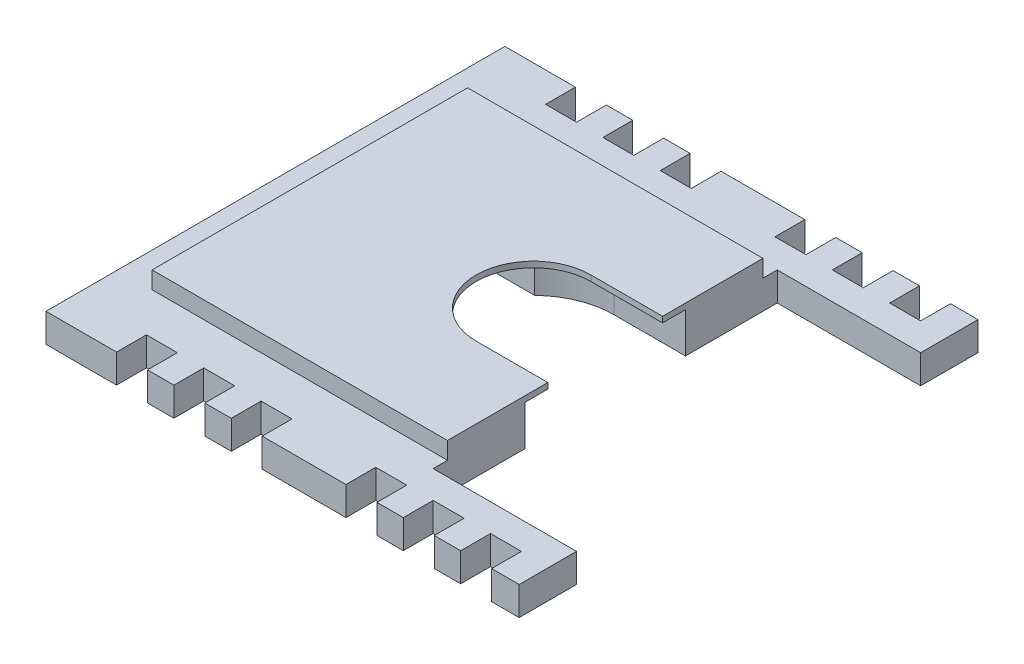
SolidWorks part; units mm, degrees
ref_plane "Front Plane" through (0, 0, 0) normal (0, 0, 1) x (1, 0, 0)
ref_plane "Top Plane" through (0, 0, 0) normal (0, 1, 0) x (1, 0, 0)
ref_plane "Right Plane" through (0, 0, 0) normal (1, 0, 0) x (0, 0, -1)
sketch "Sketch1" plane through (0, 0, 0) normal (0, 1, 0) x (1, 0, 0)
  line L0 (0, -50.8) -> (0, 50.8)
  line L16 (79.375, 34.925) -> (79.375, -34.925)
  line L17 (0, 0) -> (12.404, 0) construction
  line L18 (117.475, 34.925) -> (117.475, 0) construction
  line L19 (104.775, 50.8) -> (104.775, 34.925)
  line L20 (104.775, -34.925) -> (79.375, -34.925)
  line L21 (104.775, -50.8) -> (104.775, -34.925)
  line L22 (98.425, -50.8) -> (104.775, -50.8)
  line L23 (98.425, -44.45) -> (98.425, -50.8)
  line L24 (92.075, -44.45) -> (98.425, -44.45)
  line L25 (92.075, -50.8) -> (92.075, -44.45)
  line L26 (85.725, -50.8) -> (92.075, -50.8)
  line L27 (85.725, -44.45) -> (85.725, -50.8)
  line L29 (28.575, -50.8) -> (28.575, -44.45)
  line L30 (22.225, -50.8) -> (28.575, -50.8)
  line L31 (22.225, -44.45) -> (22.225, -50.8)
  line L32 (15.875, -44.45) -> (22.225, -44.45)
  line L33 (15.875, -50.8) -> (15.875, -44.45)
  line L34 (0, -50.8) -> (15.875, -50.8)
  line L35 (28.575, -44.45) -> (34.925, -44.45)
  line L36 (34.925, -44.45) -> (34.925, -50.8)
  line L37 (34.925, -50.8) -> (41.275, -50.8)
  line L38 (41.275, -50.8) -> (41.275, -44.45)
  line L39 (41.275, -44.45) -> (47.625, -44.45)
  line L40 (79.375, -44.45) -> (79.375, -50.8)
  line L41 (79.375, -50.8) -> (73.025, -50.8)
  line L42 (73.025, -50.8) -> (73.025, -44.45)
  line L43 (79.375, -44.45) -> (85.725, -44.45)
  line L44 (47.625, -44.45) -> (47.625, -50.8)
  line L45 (47.625, -50.8) -> (66.675, -50.8)
  line L46 (66.675, -50.8) -> (66.675, -44.45)
  line L47 (66.675, -44.45) -> (73.025, -44.45)
  line L48 (0, 50.8) -> (15.875, 50.8)
  line L49 (104.775, 34.925) -> (79.375, 34.925)
  line L50 (66.675, 44.45) -> (73.025, 44.45)
  line L51 (66.675, 50.8) -> (66.675, 44.45)
  line L52 (47.625, 50.8) -> (66.675, 50.8)
  line L53 (47.625, 44.45) -> (47.625, 50.8)
  line L54 (79.375, 44.45) -> (85.725, 44.45)
  line L55 (73.025, 50.8) -> (73.025, 44.45)
  line L56 (79.375, 50.8) -> (73.025, 50.8)
  line L57 (79.375, 44.45) -> (79.375, 50.8)
  line L58 (41.275, 44.45) -> (47.625, 44.45)
  line L59 (41.275, 50.8) -> (41.275, 44.45)
  line L60 (34.925, 50.8) -> (41.275, 50.8)
  line L61 (34.925, 44.45) -> (34.925, 50.8)
  line L62 (28.575, 44.45) -> (34.925, 44.45)
  line L63 (15.875, 50.8) -> (15.875, 44.45)
  line L64 (15.875, 44.45) -> (22.225, 44.45)
  line L65 (22.225, 44.45) -> (22.225, 50.8)
  line L66 (22.225, 50.8) -> (28.575, 50.8)
  line L67 (28.575, 50.8) -> (28.575, 44.45)
  line L68 (85.725, 44.45) -> (85.725, 50.8)
  line L69 (85.725, 50.8) -> (92.075, 50.8)
  line L70 (92.075, 50.8) -> (92.075, 44.45)
  line L71 (92.075, 44.45) -> (98.425, 44.45)
  line L72 (98.425, 44.45) -> (98.425, 50.8)
  line L73 (98.425, 50.8) -> (104.775, 50.8)
  circle A0 centre (57.15, 0) radius 12.7
  point P24 (79.375, 0)
  point P44 (57.15, -50.8)
  dimension "D7" = 25.4
  dimension "D1" = 44.45
  dimension "D2" = 6.35
  dimension "D3" = 69.85
  dimension "D4" = 101.6
  dimension "D5" = 25.4
  dimension "D6" = 15.875
extrude "Boss-Extrude1" add sketch "Sketch1" along normal blind 6.35
sketch "Sketch3" plane through (0, 6.35, 0) normal (0, 1, 0) x (1, 0, 0)
  line L1 (79.375, 34.925) -> (7.62, 34.925)
  line L2 (79.375, 34.925) -> (79.375, -34.925)
  line L3 (79.375, -34.925) -> (7.62, -34.925)
  line L4 (7.62, 34.925) -> (7.62, -34.925)
  line L5 (104.775, -34.925) -> (79.375, -34.925) construction
  line L6 (0, 50.8) -> (0, -50.8) construction
  circle A0 centre (57.15, 0) radius 17.78
  dimension "D2" = 35.56
  dimension "D1" = 7.62
extrude "Boss-Extrude2" add sketch "Sketch3" along normal blind 2.54
sketch "Sketch4" plane through (0, 0, 0) normal (0, -1, 0) x (1, 0, 0)
  circle A0 centre (57.15, 0) radius 17.78
  dimension "D1" = 35.56
extrude "Cut-Extrude1" cut sketch "Sketch4" against normal offset from surface (6.35 mm away) 2.54 up to face at (43.4975, 8.89, 0)
sketch "Sketch5" plane through (0, 0, 0) normal (0, -1, 0) x (-1, 0, 0)
  line L0 (-22.225, 44.45) -> (-15.875, 44.45) construction
  line L1 (-15.621, 51.054) -> (-22.479, 51.054)
  line L2 (-15.621, 51.054) -> (-15.621, 44.196)
  line L3 (-15.621, 44.196) -> (-22.479, 44.196)
  line L4 (-22.479, 51.054) -> (-22.479, 44.196)
  line L5 (-15.621, 51.054) -> (-22.479, 44.196) construction
  line L6 (-15.621, 44.196) -> (-22.479, 51.054) construction
  line L7 (-15.875, 44.45) -> (-15.875, 50.8) construction
  line L8 (-28.321, 51.054) -> (-35.179, 51.054)
  line L9 (-28.321, 51.054) -> (-28.321, 44.196)
  line L10 (-28.321, 44.196) -> (-35.179, 44.196)
  line L11 (-35.179, 51.054) -> (-35.179, 44.196)
  line L12 (-28.321, 51.054) -> (-35.179, 44.196) construction
  line L13 (-28.321, 44.196) -> (-35.179, 51.054) construction
  line L14 (-41.021, 51.054) -> (-47.879, 51.054)
  line L15 (-41.021, 51.054) -> (-41.021, 44.196)
  line L16 (-41.021, 44.196) -> (-47.879, 44.196)
  line L17 (-47.879, 51.054) -> (-47.879, 44.196)
  line L18 (-41.021, 51.054) -> (-47.879, 44.196) construction
  line L19 (-41.021, 44.196) -> (-47.879, 51.054) construction
  line L20 (-66.421, 51.054) -> (-73.279, 51.054)
  line L21 (-66.421, 51.054) -> (-66.421, 44.196)
  line L22 (-66.421, 44.196) -> (-73.279, 44.196)
  line L23 (-73.279, 51.054) -> (-73.279, 44.196)
  line L24 (-79.121, 51.054) -> (-85.979, 51.054)
  line L25 (-79.121, 51.054) -> (-79.121, 44.196)
  line L26 (-79.121, 44.196) -> (-85.979, 44.196)
  line L27 (-85.979, 51.054) -> (-85.979, 44.196)
  line L28 (-91.821, 51.054) -> (-98.679, 51.054)
  line L29 (-91.821, 51.054) -> (-91.821, 44.196)
  line L30 (-91.821, 44.196) -> (-98.679, 44.196)
  line L31 (-98.679, 51.054) -> (-98.679, 44.196)
  line L32 (-66.421, 51.054) -> (-73.279, 44.196) construction
  line L33 (-66.421, 44.196) -> (-73.279, 51.054) construction
  line L34 (-79.121, 51.054) -> (-85.979, 44.196) construction
  line L35 (-79.121, 44.196) -> (-85.979, 51.054) construction
  line L36 (-91.821, 51.054) -> (-98.679, 44.196) construction
  line L37 (-91.821, 44.196) -> (-98.679, 51.054) construction
  line L38 (0, 0) -> (-20.6098, 0) construction
  line L39 (-91.821, -44.196) -> (-98.679, -51.054) construction
  line L40 (-91.821, -51.054) -> (-98.679, -44.196) construction
  line L41 (-79.121, -44.196) -> (-85.979, -51.054) construction
  line L42 (-79.121, -51.054) -> (-85.979, -44.196) construction
  line L43 (-66.421, -44.196) -> (-73.279, -51.054) construction
  line L44 (-66.421, -51.054) -> (-73.279, -44.196) construction
  line L45 (-41.021, -44.196) -> (-47.879, -51.054) construction
  line L46 (-41.021, -51.054) -> (-47.879, -44.196) construction
  line L47 (-28.321, -44.196) -> (-35.179, -51.054) construction
  line L48 (-28.321, -51.054) -> (-35.179, -44.196) construction
  line L49 (-15.621, -44.196) -> (-22.479, -51.054) construction
  line L50 (-15.621, -51.054) -> (-22.479, -44.196) construction
  line L51 (-98.679, -51.054) -> (-98.679, -44.196)
  line L52 (-91.821, -44.196) -> (-98.679, -44.196)
  line L53 (-91.821, -51.054) -> (-91.821, -44.196)
  line L54 (-91.821, -51.054) -> (-98.679, -51.054)
  line L55 (-85.979, -51.054) -> (-85.979, -44.196)
  line L56 (-79.121, -44.196) -> (-85.979, -44.196)
  line L57 (-79.121, -51.054) -> (-79.121, -44.196)
  line L58 (-79.121, -51.054) -> (-85.979, -51.054)
  line L59 (-73.279, -51.054) -> (-73.279, -44.196)
  line L60 (-66.421, -44.196) -> (-73.279, -44.196)
  line L61 (-66.421, -51.054) -> (-66.421, -44.196)
  line L62 (-66.421, -51.054) -> (-73.279, -51.054)
  line L63 (-47.879, -51.054) -> (-47.879, -44.196)
  line L64 (-41.021, -44.196) -> (-47.879, -44.196)
  line L65 (-41.021, -51.054) -> (-41.021, -44.196)
  line L66 (-41.021, -51.054) -> (-47.879, -51.054)
  line L67 (-35.179, -51.054) -> (-35.179, -44.196)
  line L68 (-28.321, -44.196) -> (-35.179, -44.196)
  line L69 (-28.321, -51.054) -> (-28.321, -44.196)
  line L70 (-28.321, -51.054) -> (-35.179, -51.054)
  line L71 (-22.479, -51.054) -> (-22.479, -44.196)
  line L72 (-15.621, -44.196) -> (-22.479, -44.196)
  line L73 (-15.621, -51.054) -> (-15.621, -44.196)
  line L74 (-15.621, -51.054) -> (-22.479, -51.054)
  point P0 (-19.05, 47.625)
  point P7 (-19.05, 44.45)
  point P10 (-15.875, 47.625)
  point P12 (-31.75, 47.625)
  point P17 (-44.45, 47.625)
  point P22 (-69.85, 47.625)
  point P27 (-82.55, 47.625)
  point P32 (-95.25, 47.625)
  point P63 (-95.25, -47.625)
  point P64 (-82.55, -47.625)
  point P65 (-69.85, -47.625)
  point P66 (-44.45, -47.625)
  point P67 (-31.75, -47.625)
  point P68 (-19.05, -47.625)
  dimension "D1" = 6.858
  dimension "D2" = 3
  dimension "D3" = 2
extrude "Cut-Extrude2" cut sketch "Sketch5" against normal through all
sketch "Sketch7" plane through (0, 8.89, 0) normal (0, 1, 0) x (1, 0, 0)
  line L0 (79.375, -34.925) -> (79.375, 34.925) construction
  line L1 (7.62, 34.925) -> (79.375, 34.925)
  line L2 (7.62, 34.925) -> (7.62, -34.925)
  line L3 (7.62, -34.925) -> (79.375, -34.925)
  line L4 (79.375, 34.925) -> (79.375, -34.925)
  line L5 (7.62, -34.925) -> (79.375, -34.925) construction
  circle A0 centre (57.15, 0) radius 12.7
  dimension "D1" = 25.4
extrude "Boss-Extrude3" add sketch "Sketch7" along normal blind 1.27
sketch "Sketch8" plane through (0, 10.16, 0) normal (0, 1, 0) x (1, 0, 0)
  line L0 (57.15, 12.7) -> (79.375, 12.7)
  line L1 (79.375, -34.925) -> (79.375, 34.925) construction
  line L2 (79.375, 12.7) -> (79.375, -12.7)
  line L3 (79.375, -12.7) -> (57.15, -12.7)
  line L4 (57.15, -12.7) -> (57.15, 12.7)
  line L5 (47.879, -50.8) -> (66.421, -50.8) construction
  circle A0 centre (57.15, 0) radius 12.7 construction
  point P11 (57.15, -50.8)
extrude "Cut-Extrude4" cut sketch "Sketch8" against normal through all
sketch "Sketch9" plane through (0, 0, 0) normal (0, -1, 0) x (1, 0, 0)
  line L0 (57.15, 17.78) -> (57.15, 12.7)
  line L1 (25.4, -12.7) -> (57.15, -12.7)
  line L2 (25.4, -12.7) -> (25.4, 12.7)
  line L3 (25.4, 12.7) -> (57.15, 12.7)
  line L5 (47.879, 50.8) -> (66.421, 50.8) construction
  line L6 (57.15, 17.78) -> (79.375, 17.78)
  line L7 (79.375, 34.925) -> (79.375, 12.7) construction
  line L8 (57.15, -12.7) -> (57.15, -17.78)
  line L9 (57.15, -17.78) -> (79.375, -17.78)
  line L10 (79.375, -12.7) -> (79.375, -34.925) construction
  line L11 (79.375, -17.78) -> (79.375, 17.78)
  arc A0 (69.5934, 12.7) -> (69.5934, -12.7) centre (57.15, 0) ccw construction
  arc A1 (69.5934, 12.7) -> (69.5934, -12.7) centre (57.15, 0) ccw construction
  point P4 (25.4, 0)
  point P14 (57.15, 50.8)
  dimension "D1" = 25.4
  dimension "D3" = 25.4
extrude "Cut-Extrude5" cut sketch "Sketch9" against normal up to surface (8.89 mm away) up to face at (52.6409, 8.89, 0)
sketch "Sketch10" plane through (0, 6.35, 0) normal (0, 1, 0) x (1, 0, 0)
  line L0 (104.775, 34.925) -> (104.775, 50.8) construction
  line L1 (104.775, 38.1) -> (73.025, 38.1)
  line L2 (104.775, 38.1) -> (104.775, -38.1)
  line L3 (104.775, -38.1) -> (73.025, -38.1)
  line L4 (73.025, 38.1) -> (73.025, -38.1)
  point P6 (104.775, 0)
  dimension "D1" = 76.2
  dimension "D2" = 31.75
extrude "Cut-Extrude6" cut sketch "Sketch10" against normal through all both and the other way through all
